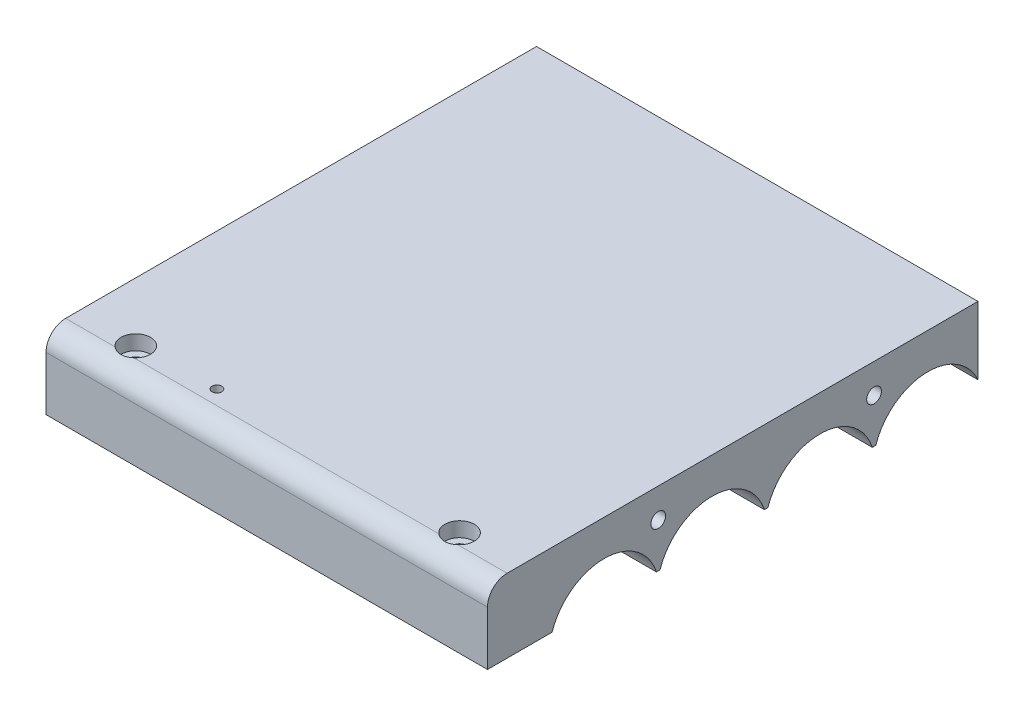
SolidWorks part; units mm, degrees
ref_plane "前视基准面" through (0, 0, 0) normal (0, 0, 1) x (1, 0, 0)
ref_plane "上视基准面" through (0, 0, 0) normal (0, 1, 0) x (1, 0, 0)
ref_plane "右视基准面" through (0, 0, 0) normal (1, 0, 0) x (0, 0, -1)
other "Configuration Table"
sketch "草图1" plane through (0, 0, 0) normal (0, 1, 0) x (1, 0, 0)
  line L1 (0, 0) -> (70, 0)
  line L2 (0, 0) -> (0, 110)
  line L3 (0, 110) -> (70, 110)
  line L4 (70, 0) -> (70, 110)
  dimension "D1" = 110
  dimension "D2" = 70
extrude "凸台-拉伸1" add sketch "草图1" along normal blind 5
sketch "草图2" plane through (0, 0, 0) normal (-1, 0, 0) x (0, 0, 1)
  line L0 (-100.81, -13.5) -> (-110, -13.5)
  line L1 (-12.81, -13.5) -> (-12.81, 0)
  line L2 (-110, -13.5) -> (-110, 0)
  line L4 (-110, 0) -> (0, 0)
  line L5 (0, 0) -> (0, 5)
  line L6 (0, 5) -> (-110, 5)
  line L7 (-110, 5) -> (-110, 0)
  line L8 (-110, 0) -> (0, 0)
  line L9 (0, 0) -> (0, 5)
  line L10 (0, 5) -> (-110, 5)
  line L11 (-110, 5) -> (-110, 0)
  circle A4 centre (-23.81, -13.5) radius 11
  circle A5 centre (-45.81, -13.5) radius 11
  circle A6 centre (-67.81, -13.5) radius 11
  circle A7 centre (-89.81, -13.5) radius 11
  line M5 (-110, 0) -> (0, 0)
  dimension "D1" = 0
extrude "凸台-拉伸2" add sketch "草图2" against normal up to surface (70 mm away) contours A7 A6 A5 A4 L1 M5 region at (0, -12.5188, -105.405) up to face at (70, 2.5, -55)
sketch "草图3" plane through (0, 0, 0) normal (-1, 0, 0) x (0, 0, 1)
  line L0 (-110, -10) -> (-12.81, -10)
  line L1 (-110, 5) -> (-110, -13.5) construction
  line L2 (-12.81, -13.5) -> (-12.81, 0) construction
  line L3 (-110, 5) -> (0, 5) construction
  line L4 (-12.81, 0) -> (-12.81, 5)
  line L9 (-110, 5) -> (-110, -13.5)
  line L10 (-12.81, -13.5) -> (-12.81, 0)
  line L11 (-12.81, 0) -> (0, 0)
  line L12 (0, 0) -> (0, 5)
  line L13 (0, 5) -> (-110, 5)
  line L14 (-110, 5) -> (-110, -13.5)
  line L15 (-12.81, -13.5) -> (-12.81, 0)
  line L16 (-12.81, 0) -> (0, 0)
  line L17 (0, 0) -> (0, 5)
  line L18 (0, 5) -> (-110, 5)
  line L21 (-110, -13.5) -> (-100.81, -13.5)
  line L23 (-110, -13.5) -> (-100.81, -13.5)
  arc A4 (-78.81, -13.5) -> (-100.81, -13.5) centre (-89.81, -13.5) ccw
  arc A5 (-56.81, -13.5) -> (-78.81, -13.5) centre (-67.81, -13.5) ccw
  arc A6 (-34.81, -13.5) -> (-56.81, -13.5) centre (-45.81, -13.5) ccw
  arc A7 (-12.81, -13.5) -> (-34.81, -13.5) centre (-23.81, -13.5) ccw
  arc A8 (-78.81, -13.5) -> (-100.81, -13.5) centre (-89.81, -13.5) ccw
  arc A9 (-56.81, -13.5) -> (-78.81, -13.5) centre (-67.81, -13.5) ccw
  arc A10 (-34.81, -13.5) -> (-56.81, -13.5) centre (-45.81, -13.5) ccw
  arc A11 (-12.81, -13.5) -> (-34.81, -13.5) centre (-23.81, -13.5) ccw
  line M11 (-110, 5) -> (-110, -13.5)
  arc M12 (-100.81, -13.5) -> (-78.81, -13.5) centre (-89.81, -13.5) cw
  arc M13 (-78.81, -13.5) -> (-56.81, -13.5) centre (-67.81, -13.5) cw
  arc M14 (-56.81, -13.5) -> (-34.81, -13.5) centre (-45.81, -13.5) cw
  arc M15 (-34.81, -13.5) -> (-12.81, -13.5) centre (-23.81, -13.5) cw
  line M16 (-12.81, -13.5) -> (-12.81, 0)
  dimension "D1" = 15
  dimension "D2" = 0
extrude "切除-拉伸1" cut sketch "草图3" against normal up to surface (70 mm away) contours L0 M11 M12 | L0 M12 M13 | L0 M13 M14 | L0 M14 M15 | L0 M15 M16 region at (0, -11.7323, -105.3092) region at (0, -10.8704, -78.81) region at (0, -10.8704, -56.81) region at (0, -10.8704, -12.9807) region at (0, -10.8704, -34.81) up to face at (70, -2.7, -51.686)
sketch "草图4" plane through (0, 0, 0) normal (-1, 0, 0) x (0, 0, 1)
  line L0 (-12.81, -10) -> (0, -10)
  line L1 (0, -10) -> (0, 0)
  line L2 (-12.81, -10) -> (-12.81, 0) construction
  line L3 (-12.81, 0) -> (0, 0) construction
  line L4 (-12.81, 0) -> (0, 0)
  line L5 (-12.81, -10) -> (-12.81, 0)
extrude "凸台-拉伸3" add sketch "草图4" against normal up to surface (70 mm away) up to face at (70, -4.2857, -50.0071)
sketch "草图5" plane through (0, 0, 0) normal (-1, 0, 0) x (0, 0, 1)
  line L0 (-110, -10) -> (-100.2383, -10) construction
  line L1 (-110, 5) -> (-100, 5)
  line L2 (-110, 5) -> (-110, -10)
  line L3 (-110, -10) -> (-100, -10)
  line L4 (-100, 5) -> (-100, -10)
  dimension "D1" = 10
extrude "切除-拉伸2" cut sketch "草图5" against normal up to surface (70 mm away) up to face at (70, -5, -56.2067)
sketch "草图6" plane through (0, 0, 0) normal (-1, 0, 0) x (0, 0, 1)
  circle A0 centre (-89.81, -13.5) radius 11.2
  arc A1 (-79.3817, -10) -> (-100, -9.357) centre (-89.81, -13.5) ccw construction
  circle A2 centre (-67.81, -13.5) radius 11.2
  circle A3 centre (-45.81, -13.5) radius 11.2
  circle A4 centre (-23.81, -13.5) radius 11.2
  dimension "D1" = 22.4
  dimension "D2" = 4
extrude "切除-拉伸3" cut sketch "草图6" against normal up to next contours A0 | A2 | A3 | A4
sketch "草图7" plane through (70, 0, 0) normal (1, 0, 0) x (0, 0, -1)
  circle A2 centre (78.81, -1) radius 1.5
  circle A3 centre (34.81, -1) radius 1.5
  dimension "D1" = 3
extrude "切除-拉伸4" cut sketch "草图7" against normal blind 10
sketch "草图8" plane through (0, 0, 0) normal (-1, 0, 0) x (0, 0, 1)
  line L0 (-100, -8.852) -> (-100, 5) construction
  line L1 (0, 5) -> (-100, 5)
  line L2 (0, 5) -> (0, -2.3)
  line L3 (-12.61, -2.3) -> (-100, -2.3)
  line L4 (-100, 5) -> (-100, -2.3)
  line L5 (-13.1709, -10) -> (0, -10) construction
  line L7 (0, -2.3) -> (0, -10)
  line L8 (0, -10) -> (-12.61, -10)
  line L9 (-12.61, -2.3) -> (-12.61, -10)
  dimension "D1" = 7.3
  dimension "D2" = 12.61
extrude "凸台-拉伸4" add sketch "草图8" along normal blind 20
sketch "草图9" plane through (0, 0, -100) normal (0, 0, -1) x (-1, 0, 0)
  circle A2 centre (8, 1.35) radius 1.5
  circle A3 centre (-58, 1.35) radius 1.5
  dimension "D1" = 3
extrude "切除-拉伸5" cut sketch "草图9" against normal blind 10 contours A3 | A2 region at (-8, 1.35, -100) region at (58, 1.35, -100)
sketch "草图10" plane through (0, 5, 0) normal (0, 1, 0) x (1, 0, 0)
  line L0 (-20, 12.61) -> (0, 12.61) construction
  line L1 (-20, 12.61) -> (-20, 0) construction
  line L2 (-20, 6.305) -> (70, 6.305) construction
  line L3 (70, 0) -> (70, 100) construction
  circle A0 centre (-8, 6.305) radius 1.5
  circle A1 centre (58, 6.305) radius 1.5
  dimension "D1" = 12
  dimension "D3" = 3
  dimension "D2" = 12
extrude "切除-拉伸6" cut sketch "草图10" against normal up to next
sketch "草图11" plane through (0, 5, 0) normal (0, 1, 0) x (1, 0, 0)
  circle A0 centre (-8, 6.305) radius 3
  circle A1 centre (58, 6.305) radius 3
  dimension "D1" = 6
extrude "切除-拉伸7" cut sketch "草图11" against normal blind 3
sketch "草图12" plane through (0, 5, 0) normal (0, 1, 0) x (1, 0, 0)
  circle A1 centre (7.891, 6.9433) radius 1
extrude "切除-拉伸8" cut sketch "草图12" against normal up to next
fillet "圆角1" radius 4 1 edges at (25, 5, 0)
sketch "草图13" plane through (-20, 0, 0) normal (-1, 0, 0) x (0, 0, 1)
  line L0 (-100, 1.35) -> (-55, 1.35) construction
  line L1 (-100, 5) -> (-100, -2.3) construction
  line L2 (0, -10) -> (0, 1) construction
  circle A0 centre (-55, 1.35) radius 1.5
  dimension "D1" = 3
  dimension "D2" = 55
extrude "切除-拉伸9" cut sketch "草图13" against normal blind 10
